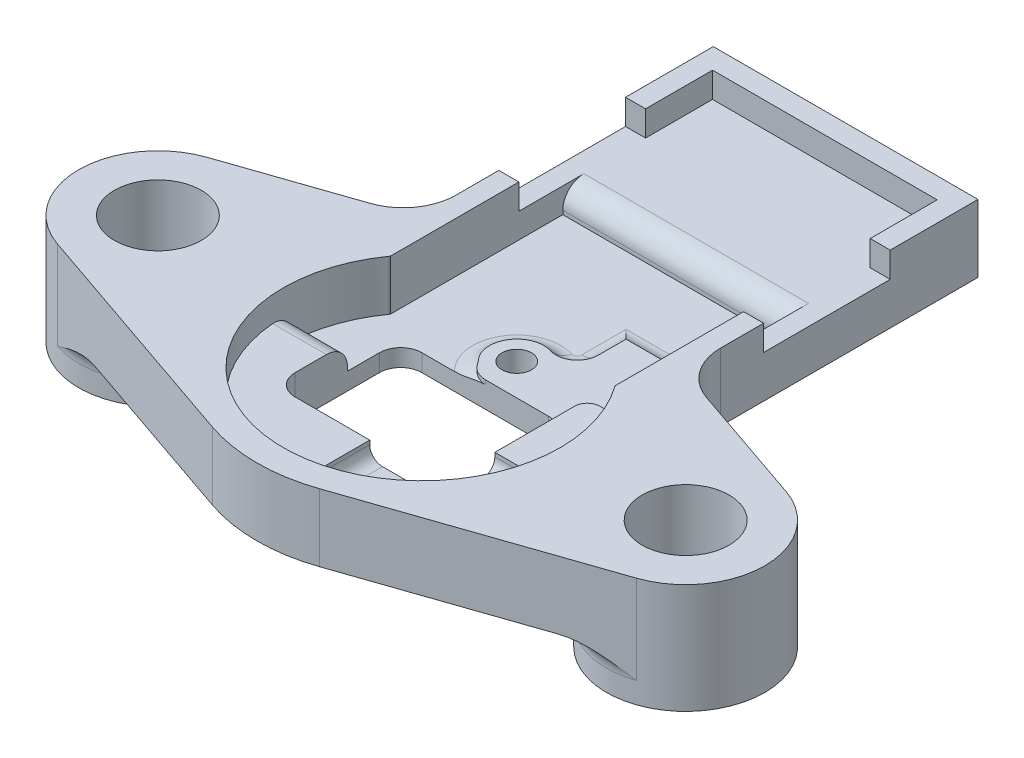
SolidWorks part; units mm, degrees
ref_plane "Front Plane" through (0, 0, 0) normal (0, 0, 1) x (1, 0, 0)
ref_plane "Top Plane" through (0, 0, 0) normal (0, 1, 0) x (1, 0, 0)
ref_plane "Right Plane" through (0, 0, 0) normal (1, 0, 0) x (0, 0, -1)
sketch "Sketch1" plane through (0, 0, 0) normal (0, -1, 0) x (1, 0, 0)
  line L6 (6.3754, -15.4686) -> (6.3754, -6.1404)
  line L7 (-6.3754, -15.4686) -> (6.3754, -15.4686)
  line L8 (-6.3754, -6.1404) -> (-6.3754, -15.4686)
  line L20 (17.4219, 4.5043) -> (3.2216, 9.3809)
  line L21 (-3.2216, 9.3809) -> (-17.4219, 4.5043)
  line L22 (-17.4219, -4.5043) -> (-10.1067, -7.0165)
  line L23 (-7.9629, -10.0193) -> (-7.9629, -14.7701)
  line L24 (-5.6769, -17.0561) -> (5.6769, -17.0561)
  line L25 (7.9629, -14.7701) -> (7.9629, -10.0193)
  line L26 (10.1067, -7.0165) -> (17.4219, -4.5043)
  circle A2 centre (15.875, 0) radius 2.6162
  arc A6 (6.7965, -4.8183) -> (-6.7965, -4.8183) centre (0, 0) ccw
  arc A7 (6.7965, -4.8183) -> (6.3754, -6.1404) centre (8.6614, -6.1404) ccw
  arc A8 (-6.3754, -6.1404) -> (-6.7965, -4.8183) centre (-8.6614, -6.1404) ccw
  circle A10 centre (-15.875, 0) radius 2.6162
  arc A24 (3.2216, 9.3809) -> (-3.2216, 9.3809) centre (0, 0) ccw
  arc A25 (-17.4219, 4.5043) -> (-17.4219, -4.5043) centre (-15.875, 0) ccw
  arc A26 (-7.9629, -10.0193) -> (-10.1067, -7.0165) centre (-11.1379, -10.0193) ccw
  arc A27 (-7.9629, -14.7701) -> (-5.6769, -17.0561) centre (-5.6769, -14.7701) ccw
  arc A28 (5.6769, -17.0561) -> (7.9629, -14.7701) centre (5.6769, -14.7701) ccw
  arc A29 (10.1067, -7.0165) -> (7.9629, -10.0193) centre (11.1379, -10.0193) ccw
  arc A30 (17.4219, -4.5043) -> (17.4219, 4.5043) centre (15.875, 0) ccw
extrude "Boss-Extrude1" add sketch "Sketch1" along normal blind 6.604
sketch "Sketch2" plane through (0, -6.604, 0) normal (0, -1, 0) x (1, 0, 0)
  line L3 (6.3754, -15.4686) -> (6.3754, -6.1404)
  line L4 (-6.3754, -15.4686) -> (6.3754, -15.4686)
  line L5 (-6.3754, -6.1404) -> (-6.3754, -15.4686)
  line L6 (6.3754, -15.4686) -> (6.3754, -6.1404)
  line L7 (-6.3754, -15.4686) -> (6.3754, -15.4686)
  line L8 (-6.3754, -6.1404) -> (-6.3754, -15.4686)
  arc A3 (6.7965, -4.8183) -> (-6.7965, -4.8183) centre (0, 0) ccw
  arc A4 (6.7965, -4.8183) -> (6.3754, -6.1404) centre (8.6614, -6.1404) ccw
  arc A5 (-6.3754, -6.1404) -> (-6.7965, -4.8183) centre (-8.6614, -6.1404) ccw
  arc A6 (6.7965, -4.8183) -> (-6.7965, -4.8183) centre (0, 0) ccw
  arc A7 (6.7965, -4.8183) -> (6.3754, -6.1404) centre (8.6614, -6.1404) ccw
  arc A8 (-6.3754, -6.1404) -> (-6.7965, -4.8183) centre (-8.6614, -6.1404) ccw
  dimension "D1" = 0
extrude "Boss-Extrude2" add sketch "Sketch2" against normal blind 5.08
sketch "Sketch3" plane through (0, -6.604, 0) normal (0, -1, 0) x (1, 0, 0)
  line L7 (17.4219, 4.5043) -> (3.2216, 9.3809)
  line L8 (-3.2216, 9.3809) -> (-17.4219, 4.5043)
  line L9 (-17.4219, -4.5043) -> (-10.1067, -7.0165)
  line L10 (-7.9629, -10.0193) -> (-7.9629, -14.7701)
  line L11 (-5.6769, -17.0561) -> (5.6769, -17.0561)
  line L12 (7.9629, -14.7701) -> (7.9629, -10.0193)
  line L13 (10.1067, -7.0165) -> (17.4219, -4.5043)
  line L14 (17.4219, 4.5043) -> (3.2216, 9.3809)
  line L15 (-3.2216, 9.3809) -> (-17.4219, 4.5043)
  line L16 (-17.4219, -4.5043) -> (-10.1067, -7.0165)
  line L17 (-7.9629, -10.0193) -> (-7.9629, -14.7701)
  line L18 (-5.6769, -17.0561) -> (5.6769, -17.0561)
  line L19 (7.9629, -14.7701) -> (7.9629, -10.0193)
  line L20 (10.1067, -7.0165) -> (17.4219, -4.5043)
  circle A0 centre (-15.875, 0) radius 4.7625
  circle A1 centre (15.875, 0) radius 2.6162
  circle A2 centre (15.875, 0) radius 2.6162
  circle A3 centre (-15.875, 0) radius 2.6162
  circle A4 centre (-15.875, 0) radius 2.6162
  circle A5 centre (15.875, 0) radius 4.7625
  arc A6 (17.4219, -4.5043) -> (17.4219, 4.5043) centre (15.875, 0) ccw construction
  arc A7 (-17.4219, 4.5043) -> (-17.4219, -4.5043) centre (-15.875, 0) ccw construction
  arc A8 (17.4219, -4.5043) -> (17.4219, 4.5043) centre (15.875, 0) ccw
  arc A9 (-17.4219, 4.5043) -> (-17.4219, -4.5043) centre (-15.875, 0) ccw
  arc A17 (17.4219, -4.5043) -> (17.4219, 4.5043) centre (15.875, 0) ccw
  arc A18 (3.2216, 9.3809) -> (-3.2216, 9.3809) centre (0, 0) ccw
  arc A19 (-17.4219, 4.5043) -> (-17.4219, -4.5043) centre (-15.875, 0) ccw
  arc A20 (-7.9629, -10.0193) -> (-10.1067, -7.0165) centre (-11.1379, -10.0193) ccw
  arc A21 (-7.9629, -14.7701) -> (-5.6769, -17.0561) centre (-5.6769, -14.7701) ccw
  arc A22 (5.6769, -17.0561) -> (7.9629, -14.7701) centre (5.6769, -14.7701) ccw
  arc A23 (10.1067, -7.0165) -> (7.9629, -10.0193) centre (11.1379, -10.0193) ccw
  arc A24 (17.4219, -4.5043) -> (17.4219, 4.5043) centre (15.875, 0) ccw
  arc A25 (3.2216, 9.3809) -> (-3.2216, 9.3809) centre (0, 0) ccw
  arc A26 (-17.4219, 4.5043) -> (-17.4219, -4.5043) centre (-15.875, 0) ccw
  arc A27 (-7.9629, -10.0193) -> (-10.1067, -7.0165) centre (-11.1379, -10.0193) ccw
  arc A28 (-7.9629, -14.7701) -> (-5.6769, -17.0561) centre (-5.6769, -14.7701) ccw
  arc A29 (5.6769, -17.0561) -> (7.9629, -14.7701) centre (5.6769, -14.7701) ccw
  arc A30 (10.1067, -7.0165) -> (7.9629, -10.0193) centre (11.1379, -10.0193) ccw
  line M19 (17.4219, 4.5043) -> (3.2216, 9.3809)
  arc M20 (3.2216, 9.3809) -> (-3.2216, 9.3809) centre (0, 0) ccw
  line M21 (-3.2216, 9.3809) -> (-17.4219, 4.5043)
  line M23 (-17.4219, -4.5043) -> (-10.1067, -7.0165)
  arc M24 (-10.1067, -7.0165) -> (-7.9629, -10.0193) centre (-11.1379, -10.0193) cw
  line M25 (-7.9629, -10.0193) -> (-7.9629, -14.7701)
  arc M26 (-7.9629, -14.7701) -> (-5.6769, -17.0561) centre (-5.6769, -14.7701) ccw
  line M27 (-5.6769, -17.0561) -> (5.6769, -17.0561)
  arc M28 (5.6769, -17.0561) -> (7.9629, -14.7701) centre (5.6769, -14.7701) ccw
  line M29 (7.9629, -14.7701) -> (7.9629, -10.0193)
  arc M30 (7.9629, -10.0193) -> (10.1067, -7.0165) centre (11.1379, -10.0193) cw
  line M31 (10.1067, -7.0165) -> (17.4219, -4.5043)
  dimension "D1" = 0
  dimension "D2" = 0
  dimension "D3" = 0
extrude "Cut-Extrude1" cut sketch "Sketch3" against normal blind 2.54 contours A5 A0 M19 M20 M21 M23 M24 M25 M26 M27 M28 M29 M30 M31 region at (0, -6.604, -2.9981)
sketch "Sketch5" plane through (0, -6.604, 0) normal (0, -1, 0) x (1, 0, 0)
  line L0 (-15.875, 0) -> (15.875, 0) construction
  circle A0 centre (0, 0) radius 12.446
  circle A1 centre (15.875, 0) radius 2.6162
  circle A2 centre (15.875, 0) radius 2.6162
  circle A3 centre (-15.875, 0) radius 2.6162
  circle A4 centre (-15.875, 0) radius 2.6162
  dimension "D3" = 24.892
  dimension "D1" = 0
  dimension "D2" = 0
extrude "Cut-Extrude2" cut sketch "Sketch5" against normal blind 1.6002
sketch "Sketch6" plane through (0, -6.604, 0) normal (0, -1, 0) x (1, 0, 0)
  line L0 (-15.875, 0) -> (15.875, 0) construction
  circle A0 centre (0, 0) radius 3.302
  circle A1 centre (15.875, 0) radius 2.6162
  circle A2 centre (15.875, 0) radius 2.6162
  circle A3 centre (-15.875, 0) radius 2.6162
  circle A4 centre (-15.875, 0) radius 2.6162
  dimension "D3" = 6.604
  dimension "D1" = 0
  dimension "D2" = 0
extrude "Cut-Extrude3" cut sketch "Sketch6" against normal through all contours A0
sketch "Sketch8" plane through (0, 0, 0) normal (0, 1, 0) x (1, 0, 0)
  line L0 (-7.9629, 10.0193) -> (-7.9629, 14.7701) construction
  line L1 (-7.9629, 11.8189) -> (7.9629, 11.8189)
  line L2 (-7.9629, 11.8189) -> (-7.9629, 19.6086)
  line L3 (-7.9629, 19.6086) -> (7.9629, 19.6086)
  line L4 (7.9629, 11.8189) -> (7.9629, 19.6086)
extrude "Cut-Extrude4" cut sketch "Sketch8" against normal through all
sketch "Sketch9" plane through (0, 0, -11.8189) normal (0, 0, -1) x (-1, 0, 0)
  line L8 (6.3754, 0) -> (6.3754, -1.524)
  line L9 (6.3754, -1.524) -> (-6.3754, -1.524)
  line L10 (-6.3754, -1.524) -> (-6.3754, 0)
  line L11 (-6.3754, 0) -> (-7.9629, 0)
  line L12 (-7.9629, 0) -> (-7.9629, -4.064)
  line L13 (-7.9629, -4.064) -> (7.9629, -4.064)
  line L14 (7.9629, -4.064) -> (7.9629, 0)
  line L15 (7.9629, 0) -> (6.3754, 0)
  line L16 (6.3754, 0) -> (6.3754, -1.524)
  line L17 (6.3754, -1.524) -> (-6.3754, -1.524)
  line L18 (-6.3754, -1.524) -> (-6.3754, 0)
  line L19 (-6.3754, 0) -> (-7.9629, 0)
  line L20 (-7.9629, 0) -> (-7.9629, -4.064)
  line L21 (-7.9629, -4.064) -> (7.9629, -4.064)
  line L22 (7.9629, -4.064) -> (7.9629, 0)
  line L23 (7.9629, 0) -> (6.3754, 0)
  dimension "D1" = 0
extrude "Boss-Extrude3" add sketch "Sketch9" along normal blind 25.4
sketch "Sketch11" plane through (0, 0, 0) normal (0, 1, 0) x (1, 0, 0)
  line L0 (-7.9629, 10.0193) -> (-7.9629, 37.2189) construction
  line L1 (7.9629, 37.2189) -> (-7.9629, 37.2189)
  line L2 (7.9629, 37.2189) -> (7.9629, 23.5)
  line L3 (7.9629, 23.5) -> (-7.9629, 23.5)
  line L4 (-7.9629, 37.2189) -> (-7.9629, 23.5)
  point P7 (0, 23.5)
  dimension "D1" = 23.5
extrude "Cut-Extrude5" cut sketch "Sketch11" against normal through all
sketch "Sketch12" plane through (0, 0, -23.5) normal (0, 0, -1) x (-1, 0, 0)
  line L1 (-7.9629, 0) -> (7.9629, 0)
  line L2 (-7.9629, 0) -> (-7.9629, -4.064)
  line L3 (-7.9629, -4.064) -> (7.9629, -4.064)
  line L4 (7.9629, 0) -> (7.9629, -4.064)
extrude "Boss-Extrude4" add sketch "Sketch12" along normal blind 2
sketch "Sketch13" plane through (0, -1.524, 0) normal (0, 1, 0) x (1, 0, 0)
  line L0 (0, 0) -> (0, 5.715) construction
  circle A0 centre (0, 5.715) radius 0.889
  dimension "D1" = 1.778
  dimension "D2" = 5.715
extrude "Cut-Extrude6" cut sketch "Sketch13" against normal through all
sketch "Sketch14" plane through (0, 0, 0) normal (0, 1, 0) x (1, 0, 0)
  line L0 (0, 0) -> (0, 15.1) construction
  line L1 (-7.9629, 10.0193) -> (-7.9629, 25.5) construction
  line L2 (-7.9629, 12.6) -> (7.9629, 12.6)
  line L3 (-7.9629, 12.6) -> (-7.9629, 20.22)
  line L4 (-7.9629, 20.22) -> (7.9629, 20.22)
  line L5 (7.9629, 12.6) -> (7.9629, 20.22)
  line L6 (7.9629, 25.5) -> (7.9629, 10.0193) construction
  circle A1 centre (0, 0) radius 3.302
  circle A4 centre (0, 0) radius 3.302 construction
  point P12 (-2.2964, 15.0153)
  point P13 (0, 0)
  line M5 (7.9629, 10.0193) -> (7.9629, 25.5)
  line M7 (-7.9629, 25.5) -> (-7.9629, 10.0193)
  line M18 (6.3754, 23.5) -> (6.3754, 6.1404)
  line M22 (-6.3754, 6.1404) -> (-6.3754, 23.5)
  dimension "D2" = 15.1
  dimension "D3" = 2.5
  dimension "D4" = 7.62
  dimension "D1" = 0
extrude "Cut-Extrude8" cut sketch "Sketch14" against normal up to surface (1.524 mm away) contours L4 L2 M22 M18 | L4 L2 M7 M22 | L4 L2 M18 M5 region at (-7.1691, 0, -16.41) region at (0, 0, -16.41) region at (7.1692, 0, -16.41) up to face at (0, -1.524, -4.826)
sketch "Sketch15" plane through (0, -1.524, 0) normal (0, 1, 0) x (1, 0, 0)
  line L1 (5.08, 3.81) -> (-5.08, 3.81)
  line L2 (5.08, 3.81) -> (5.08, -3.81)
  line L3 (5.08, -3.81) -> (-5.08, -3.81)
  line L4 (-5.08, 3.81) -> (-5.08, -3.81)
  line L5 (5.08, 3.81) -> (-5.08, -3.81) construction
  line L6 (5.08, -3.81) -> (-5.08, 3.81) construction
  point P0 (0, 0)
  dimension "D1" = 7.62
  dimension "D2" = 10.16
extrude "Cut-Extrude9" cut sketch "Sketch15" against normal through all
sketch "Sketch19" plane through (0, 0, 0) normal (0, 1, 0) x (1, 0, 0)
  line L0 (-6.3754, 23.5) -> (6.3754, 23.5) construction
  line L1 (6.7564, 2.54) -> (-6.7564, 2.54)
  line L2 (6.7564, 2.54) -> (6.7564, 23.5)
  line L3 (6.7564, 23.5) -> (-6.7564, 23.5)
  line L4 (-6.7564, 2.54) -> (-6.7564, 23.5)
  line L5 (-6.3754, 6.1404) -> (-6.3754, 12.6) construction
  point P6 (0, 2.54)
  dimension "D1" = 0.381
  dimension "D2" = 2.54
extrude "Cut-Extrude13" cut sketch "Sketch19" against normal up to surface (1.524 mm away) up to face at (0, -1.524, 0)
sketch "Sketch16" plane through (0, -1.524, 0) normal (0, 1, 0) x (1, 0, 0)
  line L0 (5.08, 3.81) -> (-5.08, 3.81) construction
  line L1 (-6.7564, 3.81) -> (2.1336, 3.81)
  line L2 (-6.7564, 3.81) -> (-6.7564, 15.24)
  line L3 (-6.7564, 15.24) -> (2.1336, 15.24)
  line L4 (2.1336, 3.81) -> (2.1336, 15.24)
  line L8 (2.1336, 15.24) -> (6.7564, 15.24)
  line L9 (2.1336, 15.24) -> (2.1336, 10.16)
  line L10 (2.1336, 10.16) -> (6.7564, 10.16)
  line L11 (6.7564, 15.24) -> (6.7564, 10.16)
  line L12 (-6.7564, 12.6) -> (-6.7564, 4.8768) construction
  line L13 (6.7564, 4.8768) -> (6.7564, 12.6) construction
  line M7 (-5.08, 3.81) -> (5.08, 3.81)
  circle M9 centre (0, 5.715) radius 0.889
  dimension "D1" = 8.89
  dimension "D2" = 11.43
  dimension "D3" = 5.08
extrude "Cut-Extrude10" cut sketch "Sketch16" against normal blind 1.5 contours L4 L3 L2 L1 M7 M9 | L11 L8 L4 L10 region at (-2.3693, -1.524, -9.6204) region at (4.445, -1.524, -12.7)
sketch "Sketch18" plane through (0, -1.524, 0) normal (0, 1, 0) x (1, 0, 0)
  line L1 (2.1336, 10.16) -> (6.7564, 10.16)
  line L2 (2.1336, 10.16) -> (2.1336, 4.8768)
  line L3 (2.1336, 4.8768) -> (6.7564, 4.8768)
  line L4 (6.7564, 10.16) -> (6.7564, 4.8768)
  line L5 (6.7564, 4.8768) -> (6.7564, 10.16) construction
  line L6 (5.08, 4.8768) -> (5.08, 3.81)
  line L7 (5.08, 3.81) -> (2.1336, 3.81)
  line L8 (2.1336, 3.81) -> (2.1336, 4.8768)
  arc A0 (6.7564, 4.8768) -> (6.7965, 4.8183) centre (8.6614, 6.1404) ccw construction
  line M7 (6.7564, 10.16) -> (2.1336, 10.16)
  line M8 (2.1336, 10.16) -> (2.1336, 3.81)
  line M9 (2.1336, 3.81) -> (5.08, 3.81)
  line M15 (6.7564, 4.8768) -> (6.7564, 10.16)
extrude "Cut-Extrude12" cut sketch "Sketch18" against normal blind 1 contours L6 L3 M8 M9 | L3 M8 M15 M7 region at (4.445, -1.524, -7.5184) region at (3.6068, -1.524, -4.3434)
sketch "Sketch20" plane through (0, 0, 0) normal (0, 1, 0) x (1, 0, 0)
  line L0 (-6.7564, 23.5) -> (-6.7564, 20.22) construction
  line L1 (6.7564, 23.5) -> (-6.7564, 23.5)
  line L2 (6.7564, 23.5) -> (6.7564, 24.25)
  line L3 (6.7564, 24.25) -> (-6.7564, 24.25)
  line L4 (-6.7564, 23.5) -> (-6.7564, 24.25)
  dimension "D1" = 0.75
extrude "Cut-Extrude14" cut sketch "Sketch20" against normal up to surface (1.524 mm away) up to face at (0, -1.524, -17.3967)
sketch "Sketch21" plane through (0, -1.524, 0) normal (0, 1, 0) x (1, 0, 0)
  line L0 (0.6831, -8.3031) -> (0.6831, -0.6831)
  line L1 (0.6831, -0.6831) -> (8.3031, -0.6831)
  arc A1 (-6.7965, 4.8183) -> (6.7965, 4.8183) centre (0, 0) ccw construction
  arc A2 (-6.7965, 4.8183) -> (6.7965, 4.8183) centre (0, 0) ccw construction
  arc A3 (-6.7965, 4.8183) -> (6.7965, 4.8183) centre (0, 0) ccw
  line M3 (5.08, 4.8768) -> (5.08, -3.81)
  line M4 (5.08, -3.81) -> (-5.08, -3.81)
  arc M9 (-6.7965, 4.8183) -> (6.7965, 4.8183) centre (0, 0) ccw
  dimension "D1" = 7.62
  dimension "D2" = 7.62
extrude "Cut-Extrude16" cut sketch "Sketch21" against normal blind 1 contours L1 L0 M3 M4 M9 region at (4.2763, -1.524, 4.5687)
sketch "Sketch23" plane through (0, -1.524, 0) normal (0, 1, 0) x (1, 0, 0)
  line L0 (-5.08, 0.6122) -> (-8.3087, 0.6122)
  line L1 (-5.08, 3.81) -> (-5.08, -3.81) construction
  line L2 (-6.7564, 3.81) -> (-6.7564, 4.8768) construction
  line L3 (-6.7564, 3.81) -> (-5.08, 3.81) construction
  line L4 (-6.7564, 3.81) -> (-6.7564, 4.8768)
  line L5 (-6.7564, 3.81) -> (-5.08, 3.81)
  line L6 (-5.08, 3.81) -> (-5.08, -3.81)
  arc A0 (-6.7965, 4.8183) -> (0.6831, -8.3031) centre (0, 0) ccw construction
  arc A1 (-6.7965, 4.8183) -> (0.6831, -8.3031) centre (0, 0) ccw
  line M3 (-5.08, -3.81) -> (-5.08, 3.81)
  line M4 (-5.08, 3.81) -> (-6.7564, 3.81)
  line M5 (-6.7564, 3.81) -> (-6.7564, 4.8768)
  arc M6 (-6.7564, 4.8768) -> (-6.7965, 4.8183) centre (-8.6614, 6.1404) cw
  arc M7 (-6.7965, 4.8183) -> (0.6831, -8.3031) centre (0, 0) ccw
extrude "Cut-Extrude17" cut sketch "Sketch23" against normal up to surface (1.5 mm away) contours L0 M3 M4 M5 M6 M7 region at (-6.5562, -1.524, -2.207) up to face at (0, -3.024, -4.826)
sketch "Sketch24" plane through (0, -3.024, 0) normal (0, 1, 0) x (1, 0, 0)
  line L0 (0.8077, 7.1412) -> (2.1336, 6.3903)
  line L1 (2.1336, 3.81) -> (2.1336, 10.16) construction
  line L2 (-1.1774, 4.5748) -> (-0.6057, 3.81)
  line L3 (-5.08, 3.81) -> (2.1336, 3.81) construction
  line L4 (-0.6057, 3.81) -> (2.1336, 3.81)
  line L5 (2.1336, 3.81) -> (2.1336, 6.3903)
  circle A0 centre (0, 5.715) radius 1.639
  circle A1 centre (0, 5.715) radius 0.889 construction
  line M6 (-5.08, 3.81) -> (2.1336, 3.81)
  line M7 (2.1336, 3.81) -> (2.1336, 10.16)
  circle M11 centre (0, 5.715) radius 0.889
  dimension "D1" = 0.75
extrude "Boss-Extrude5" add sketch "Sketch24" along normal up to surface (0.5 mm away) contours A0 L2 L0 M6 M7 | A0 M11 region at (1.4475, -3.024, -6.7249) region at (1.3759, -3.024, -6.517) up to face at (4.6567, -2.524, -6.2823)
sketch "Sketch25" plane through (0, 0, 0) normal (0, 1, 0) x (1, 0, 0)
  line L18 (-6.7564, 20.22) -> (-6.7564, 24.25)
  line L19 (-6.7564, 24.25) -> (6.7564, 24.25)
  line L20 (-6.7564, 4.8768) -> (-6.7564, 12.6)
  line L21 (-6.7564, 12.6) -> (-7.9629, 12.6)
  line L22 (-7.9629, 12.6) -> (-7.9629, 10.0193)
  line L23 (-10.1067, 7.0165) -> (-17.4219, 4.5043)
  line L24 (-17.4219, -4.5043) -> (-3.2216, -9.3809)
  line L25 (3.2216, -9.3809) -> (17.4219, -4.5043)
  line L26 (17.4219, 4.5043) -> (10.1067, 7.0165)
  line L27 (7.9629, 10.0193) -> (7.9629, 12.6)
  line L28 (7.9629, 12.6) -> (6.7564, 12.6)
  line L29 (6.7564, 12.6) -> (6.7564, 4.8768)
  line L30 (-6.7564, 4.8768) -> (-6.7564, 12.6)
  line L31 (-6.7564, 12.6) -> (-7.9629, 12.6)
  line L32 (-7.9629, 12.6) -> (-7.9629, 10.0193)
  line L33 (-10.1067, 7.0165) -> (-17.4219, 4.5043)
  line L34 (-17.4219, -4.5043) -> (-3.2216, -9.3809)
  line L35 (3.2216, -9.3809) -> (17.4219, -4.5043)
  line L36 (17.4219, 4.5043) -> (10.1067, 7.0165)
  line L37 (7.9629, 10.0193) -> (7.9629, 12.6)
  line L38 (7.9629, 12.6) -> (6.7564, 12.6)
  line L39 (6.7564, 12.6) -> (6.7564, 4.8768)
  line L40 (6.7564, 24.25) -> (6.7564, 20.22)
  line L41 (6.7564, 20.22) -> (7.9629, 20.22)
  line L42 (7.9629, 20.22) -> (7.9629, 25.5)
  line L43 (7.9629, 25.5) -> (-7.9629, 25.5)
  line L44 (-7.9629, 25.5) -> (-7.9629, 20.22)
  line L45 (-7.9629, 20.22) -> (-6.7564, 20.22)
  line L46 (-6.7564, 20.22) -> (-6.7564, 24.25)
  line L47 (-6.7564, 24.25) -> (6.7564, 24.25)
  line L48 (6.7564, 24.25) -> (6.7564, 20.22)
  line L49 (6.7564, 20.22) -> (7.9629, 20.22)
  line L50 (7.9629, 20.22) -> (7.9629, 25.5)
  line L51 (7.9629, 25.5) -> (-7.9629, 25.5)
  line L52 (-7.9629, 25.5) -> (-7.9629, 20.22)
  line L53 (-7.9629, 20.22) -> (-6.7564, 20.22)
  circle A9 centre (15.875, 0) radius 2.6162
  circle A10 centre (15.875, 0) radius 2.6162
  circle A11 centre (-15.875, 0) radius 2.6162
  circle A12 centre (-15.875, 0) radius 2.6162
  arc A20 (-6.7965, 4.8183) -> (-6.7564, 4.8768) centre (-8.6614, 6.1404) ccw
  arc A21 (-10.1067, 7.0165) -> (-7.9629, 10.0193) centre (-11.1379, 10.0193) ccw
  arc A22 (-17.4219, 4.5043) -> (-17.4219, -4.5043) centre (-15.875, 0) ccw
  arc A23 (-3.2216, -9.3809) -> (3.2216, -9.3809) centre (0, 0) ccw
  arc A24 (17.4219, -4.5043) -> (17.4219, 4.5043) centre (15.875, 0) ccw
  arc A25 (7.9629, 10.0193) -> (10.1067, 7.0165) centre (11.1379, 10.0193) ccw
  arc A26 (6.7564, 4.8768) -> (6.7965, 4.8183) centre (8.6614, 6.1404) ccw
  arc A27 (-6.7965, 4.8183) -> (6.7965, 4.8183) centre (0, 0) ccw
  arc A28 (-6.7965, 4.8183) -> (-6.7564, 4.8768) centre (-8.6614, 6.1404) ccw
  arc A29 (-10.1067, 7.0165) -> (-7.9629, 10.0193) centre (-11.1379, 10.0193) ccw
  arc A30 (-17.4219, 4.5043) -> (-17.4219, -4.5043) centre (-15.875, 0) ccw
  arc A31 (-3.2216, -9.3809) -> (3.2216, -9.3809) centre (0, 0) ccw
  arc A32 (17.4219, -4.5043) -> (17.4219, 4.5043) centre (15.875, 0) ccw
  arc A33 (7.9629, 10.0193) -> (10.1067, 7.0165) centre (11.1379, 10.0193) ccw
  arc A34 (6.7564, 4.8768) -> (6.7965, 4.8183) centre (8.6614, 6.1404) ccw
  arc A35 (-6.7965, 4.8183) -> (6.7965, 4.8183) centre (0, 0) ccw
  dimension "D1" = 0
  dimension "D2" = 0
  dimension "D3" = 0
  dimension "D4" = 0
fillet "Fillet3" radius 1.27 2 edges at (11.1125, -4.064, 0) (-11.1125, -4.064, 0)
fillet "Fillet4" radius 1.27 4 edges at (-5.08, -3.544, -3.81) (-5.08, -2.794, 3.81) (5.08, -3.294, 3.81) (5.08, -3.294, -3.81)
fillet "Fillet5" radius 1.27 1 edges at (2.1336, -2.774, -6.3903)
fillet "Fillet6" radius 1.27 1 edges at (-0.6057, -2.774, -3.81)
fillet "Fillet7" radius 1.27 3 edges at (2.1336, -3.024, -9.3264) (1.6166, -3.024, -7.4702) (-1.3961, -3.024, -6.5737)
fillet "Fillet8" radius 1.27 1 edges at (3.94, -3.024, -10.16)
fillet "Fillet9" radius 0.762 2 edges at (0.6831, -2.524, 6.0566) (6.6916, -2.524, 0.6831)
fillet "Fillet10" radius 0.762 1 edges at (5.08, -2.024, -4.8768)
fillet "Fillet11" radius 1.27 1 edges at (0, -1.524, -15.24)
fillet "Fillet12" radius 1.27 1 edges at (-6.6943, -1.524, -0.6122)
